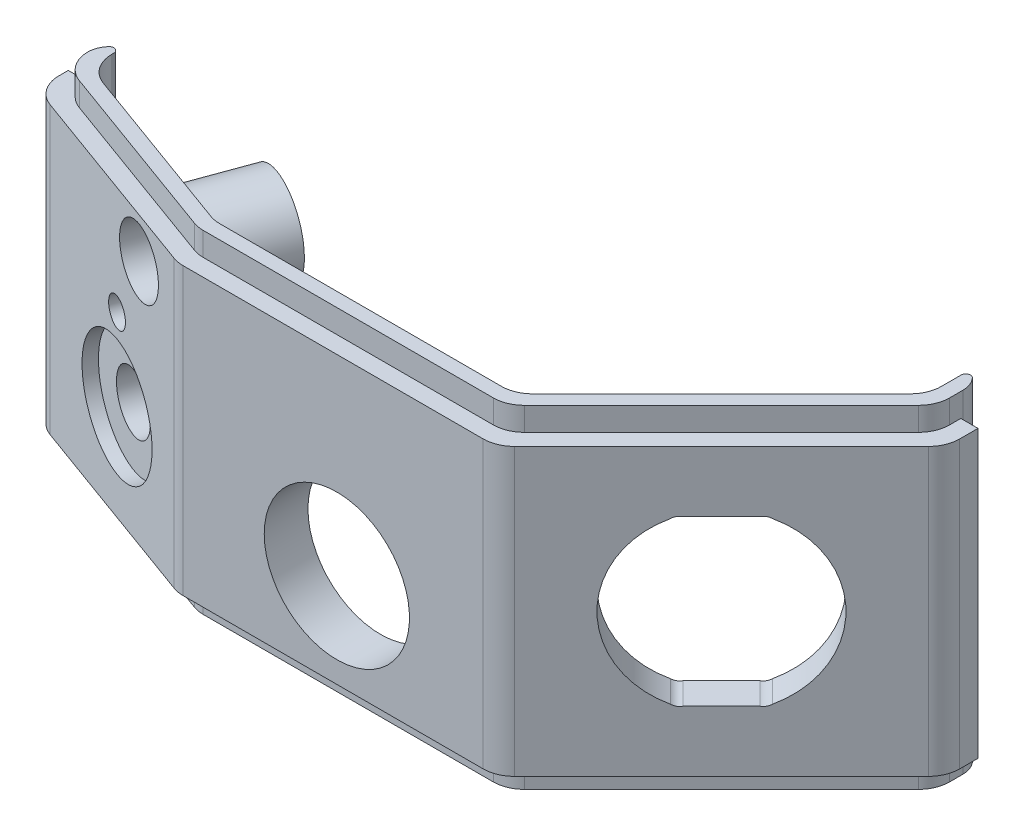
SolidWorks part; units mm, degrees
material "6061 Alloy"
ref_plane "Front Plane" through (0, 0, 0) normal (0, 0, 1) x (1, 0, 0)
ref_plane "Top Plane" through (0, 0, 0) normal (0, 1, 0) x (1, 0, 0)
ref_plane "Right Plane" through (0, 0, 0) normal (1, 0, 0) x (0, 0, -1)
sketch "Sketch1" plane through (0, 0, 0) normal (0, 1, 0) x (1, 0, 0)
  line L0 (-12.9569, 0) -> (12.9569, 0)
  line L1 (12.9569, 0) -> (31.2806, 18.3238)
  line L2 (-12.9569, 0) -> (-30.924, 6.5395)
  line L4 (28.7406, 19.3759) -> (11.9048, 2.54)
  line L5 (11.9048, 2.54) -> (-12.509, 2.54)
  line L6 (-12.509, 2.54) -> (-28.384, 8.318)
  line L8 (31.2806, 18.3238) -> (31.2806, 22.7688)
  line L9 (31.2806, 22.7688) -> (28.7406, 22.7688)
  line L10 (28.7406, 22.7688) -> (28.7406, 19.3759)
  line L11 (-28.384, 8.318) -> (-28.384, 10.9845)
  line L12 (-28.384, 10.9845) -> (-30.924, 10.9845)
  line L13 (-30.924, 10.9845) -> (-30.924, 6.5395)
  point P15 (0, 0)
  dimension "D2" = 2.54
  dimension "D3" = 135
  dimension "D6" = 4.445
  dimension "D4" = 2.54
  dimension "D7" = 2.54
  dimension "D8" = 160
  dimension "D5" = 62.2046
  dimension "D12" = 28.7406
  dimension "D13" = 4.445
  dimension "D11" = 15.875
  dimension "D9" = 17.9671
extrude "Boss-Extrude1" add sketch "Sketch1" along normal mid plane 27.305
sketch "Sketch2" plane through (0, -13.6525, 0) normal (0, -1, 0) x (1, 0, 0)
  line L9 (12.3782, -1.397) -> (30.2928, -19.3116)
  line L10 (-30.4462, -7.8523) -> (-12.7105, -1.397)
  line L11 (-12.7105, -1.397) -> (12.3782, -1.397)
  line L12 (12.3782, -1.397) -> (29.8836, -18.9024)
  line L13 (-29.527, -7.5177) -> (-12.7105, -1.397)
  line L14 (-12.7105, -1.397) -> (12.3782, -1.397)
  line L16 (-30.924, -6.5395) -> (-12.9569, 0) construction
  line L17 (-12.9569, 0) -> (12.9569, 0) construction
  line L18 (12.9569, 0) -> (31.2806, -18.3238) construction
  line L19 (-30.924, -6.5395) -> (-12.9569, 0)
  line L20 (-12.9569, 0) -> (12.9569, 0)
  line L21 (12.9569, 0) -> (31.2806, -18.3238)
  line L22 (-29.527, -7.5177) -> (-29.527, -10.9845)
  line L23 (-28.384, -10.9845) -> (-30.924, -10.9845) construction
  line L24 (-29.527, -10.9845) -> (-30.924, -10.9845)
  line L25 (-30.924, -10.9845) -> (-30.924, -6.5395)
  line L26 (31.2806, -18.3238) -> (31.2806, -22.7688)
  line L27 (31.2806, -22.7688) -> (29.8836, -22.7688)
  line L28 (31.2806, -22.7688) -> (28.7406, -22.7688) construction
  line L29 (29.8836, -22.7688) -> (29.8836, -18.9024)
  dimension "D2" = 1.397
  dimension "D1" = 1.397
extrude "Cut-Extrude1" cut sketch "Sketch2" against normal blind 2.032
sketch "Sketch17" plane through (0, -13.6525, 0) normal (0, -1, 0) x (1, 0, 0)
  line L12 (28.7406, -22.7688) -> (29.8836, -22.7688)
  line L13 (29.8836, -22.7688) -> (29.8836, -18.9024)
  line L14 (29.8836, -18.9024) -> (12.3782, -1.397)
  line L15 (12.3782, -1.397) -> (-12.7105, -1.397)
  line L16 (-12.7105, -1.397) -> (-29.527, -7.5177)
  line L17 (-29.527, -7.5177) -> (-29.527, -10.9845)
  line L18 (-29.527, -10.9845) -> (-28.384, -10.9845)
  line L19 (-28.384, -10.9845) -> (-28.384, -8.318)
  line L20 (-28.384, -8.318) -> (-12.509, -2.54)
  line L21 (-12.509, -2.54) -> (11.9048, -2.54)
  line L22 (11.9048, -2.54) -> (28.7406, -19.3759)
  line L23 (28.7406, -19.3759) -> (28.7406, -22.7688)
  line L24 (28.7406, -22.7688) -> (29.8836, -22.7688)
  line L25 (29.8836, -22.7688) -> (29.8836, -18.9024)
  line L26 (29.8836, -18.9024) -> (12.3782, -1.397)
  line L27 (12.3782, -1.397) -> (-12.7105, -1.397)
  line L28 (-12.7105, -1.397) -> (-29.527, -7.5177)
  line L29 (-29.527, -7.5177) -> (-29.527, -10.9845)
  line L30 (-29.527, -10.9845) -> (-28.384, -10.9845)
  line L31 (-28.384, -10.9845) -> (-28.384, -8.318)
  line L32 (-28.384, -8.318) -> (-12.509, -2.54)
  line L33 (-12.509, -2.54) -> (11.9048, -2.54)
  line L34 (11.9048, -2.54) -> (28.7406, -19.3759)
  line L35 (28.7406, -19.3759) -> (28.7406, -22.7688)
  dimension "D1" = 0
extrude "Cut-Extrude9" cut sketch "Sketch17" against normal blind 0.127
mirror "Mirror1" about plane through (0, 0, 0) normal (0, 1, 0) of "Cut-Extrude9", "Cut-Extrude1"
fillet "Fillet3" radius 2.54 12 edges at (29.8836, 12.573, -18.9024) (12.3782, 12.573, -1.397) (-12.7105, 12.573, -1.397) (-29.527, 12.573, -7.5177) (-29.527, -12.573, -7.5177) (-30.924, 0, -6.5395) (-12.7105, -12.573, -1.397) (-12.9569, 0, 0) (12.3782, -12.573, -1.397) (12.9569, 0, 0) (31.2806, 0, -18.3238) (29.8836, -12.573, -18.9024)
fillet "Fillet4" radius 2.54 4 edges at (-28.384, 0, -8.318) (-12.509, 0, -2.54) (11.9048, 0, -2.54) (28.7406, 0, -19.3759)
sketch "Sketch5" plane through (31.2806, 0, 0) normal (1, 0, 0) x (0, 0, -1)
  line L0 (22.7688, -11.6205) -> (19.3759, -11.6205) construction
  line L1 (22.7688, 11.6205) -> (20.8638, 11.6205)
  line L2 (22.7688, 11.6205) -> (22.7688, -11.6205)
  line L3 (22.7688, -11.6205) -> (20.8638, -11.6205)
  line L4 (20.8638, 11.6205) -> (20.8638, -11.6205)
  dimension "D1" = 1.905
extrude "Cut-Extrude4" cut sketch "Sketch5" against normal up to surface (1.397 mm away) up to face at (29.8836, 12.573, -21.3616)
sketch "Sketch6" plane through (-30.924, 0, 0) normal (-1, 0, 0) x (0, 0, 1)
  line L4 (-10.9845, 11.6205) -> (-9.0795, 11.6205)
  line L5 (-10.9845, 11.6205) -> (-10.9845, -11.6205)
  line L6 (-10.9845, -11.6205) -> (-9.0795, -11.6205)
  line L7 (-9.0795, 11.6205) -> (-9.0795, -11.6205)
  line L8 (-10.9845, 11.6205) -> (-10.9845, -11.6205) construction
  line L9 (-8.318, 11.6205) -> (-10.9845, 11.6205) construction
  line L10 (-8.318, -11.6205) -> (-10.9845, -11.6205) construction
  dimension "D1" = 1.905
extrude "Cut-Extrude5" cut sketch "Sketch6" against normal up to surface (1.397 mm away) up to face at (-29.527, 12.573, -10.1404)
sketch "Sketch32" plane through (-0.6469, 0, 1.7774) normal (0.342, 0, -0.9397) x (-0.9397, 0, -0.342)
  line L0 (27.7386, 0) -> (13.0712, 0) construction
  line L1 (27.7386, -13.5255) -> (27.7386, 13.5255) construction
  line L2 (13.0712, 13.5255) -> (13.0712, -13.5255) construction
  line L3 (20.4049, 0) -> (20.4049, -3.81) construction
  circle A0 centre (20.4049, -3.81) radius 5.9944
  dimension "D1" = 11.9888
  dimension "D2" = 3.81
extrude "Boss-Extrude4" add sketch "Sketch32" along normal blind 1.5494
hole_wizard "#12-28 Tapped Hole1" positions "Sketch12" profile "Sketch13" tap size "#12-28" standard "ANSI Inch" end condition through all
sketch "Sketch12" plane through (-0.117, 0, 0.3215) normal (-0.342, 0, 0.9397) x (0.9397, 0, 0.342)
  circle A0 centre (-20.4049, -3.81) radius 5.9944 construction
  point P0 (-20.4049, -3.81)
sketch "Sketch13" plane through (-19.2914, -3.81, -6.6574) normal (0, 1, 0) x (-0.9397, 0, -0.342)
  line L0 (0, 0) -> (0, 10.2345)
  line L1 (0, 10.2345) -> (2.3114, 10.2345)
  line L2 (2.3114, 10.2345) -> (2.3114, 0)
  line L5 (2.3114, 0) -> (0, 0)
  line L11 (0, -6.35) -> (0, 107.95) construction
  dimension "Thru Tap Drill Dia." = 4.6228
  dimension "Thru Tap Drill Depth" = 10.2345
sketch "Sketch10" plane through (-1.5157, 0, 4.1643) normal (-0.342, 0, 0.9397) x (0.9397, 0, 0.342)
  line L2 (-13.0712, -3.81) -> (-27.7386, -3.81) construction
  line L3 (-14.474, -2.411) -> (-14.474, -5.209)
  line L4 (-26.3358, -2.411) -> (-26.3358, -5.209)
  line L5 (-13.0712, 13.5255) -> (-13.0712, -13.5255) construction
  line L6 (-27.7386, -13.5255) -> (-27.7386, 13.5255) construction
  arc A0 (-14.5064, -2.1733) -> (-18.5866, 2.0351) centre (-20.4049, -3.81) ccw
  arc A1 (-19.2113, 2.8672) -> (-21.5985, 2.8672) centre (-20.4049, 2.8448) ccw
  arc A2 (-26.3034, -5.4467) -> (-14.5064, -5.4467) centre (-20.4049, -3.81) ccw
  arc A3 (-22.2233, 2.0351) -> (-26.3034, -2.1733) centre (-20.4049, -3.81) ccw
  arc A4 (-21.5985, 2.8672) -> (-22.2233, 2.0351) centre (-22.4873, 2.884) cw
  arc A5 (-19.2113, 2.8672) -> (-18.5866, 2.0351) centre (-18.3225, 2.884) ccw
  arc A6 (-14.474, -2.411) -> (-14.5064, -2.1733) centre (-15.363, -2.411) ccw
  arc A7 (-14.474, -5.209) -> (-14.5064, -5.4467) centre (-15.363, -5.209) cw
  arc A8 (-26.3358, -5.209) -> (-26.3034, -5.4467) centre (-25.4468, -5.209) ccw
  arc A9 (-26.3358, -2.411) -> (-26.3034, -2.1733) centre (-25.4468, -2.411) cw
  point P19 (-21.4256, 2.2257)
  point P24 (-14.474, -2.2948)
  point P27 (-14.474, -5.3252)
  point P30 (-26.3358, -5.3252)
  point P33 (-26.3358, -2.2948)
  point P37 (-20.4049, -3.81)
  dimension "D2" = 12.2428
  dimension "D3" = 2.3876
  dimension "D5" = 0.889
  dimension "D6" = 0.889
  dimension "D1" = 11.8618
  dimension "D4" = 6.6548
  dimension "D7" = 3.81
sketch "Sketch33" plane through (-1.5157, 0, 4.1643) normal (-0.342, 0, 0.9397) x (0.9397, 0, 0.342)
  circle A0 centre (-20.4049, -3.81) radius 4.7625
  circle A1 centre (-20.4049, 2.8448) radius 1.143
  dimension "D1" = 9.525
  dimension "D2" = 2.286
extrude "Cut-Extrude16" cut sketch "Sketch33" against normal blind 1.0414
sketch "Sketch34" plane through (0, 0, -2.54) normal (0, 0, -1) x (-1, 0, 0)
  circle A0 centre (0, -3.9751) radius 8.7503
  dimension "D1" = 17.5006
  dimension "D2" = 3.9751
extrude "Boss-Extrude5" add sketch "Sketch34" along normal blind 1.016
hole_wizard "1/2-28 Tapped Hole2" positions "Sketch19" profile "Sketch20" tap size "1/2-28" standard "ANSI Inch" end condition through all
sketch "Sketch19" plane through (0, 0, -3.556) normal (0, 0, 1) x (1, 0, 0)
  circle A0 centre (0, -3.9751) radius 8.7503 construction
  point P0 (0, -3.9751)
sketch "Sketch20" plane through (0, -3.9751, -3.556) normal (1, 0, 0) x (0, 1, 0)
  line L0 (0, 0) -> (0, 3.556)
  line L1 (0, 3.556) -> (5.9055, 3.556)
  line L2 (5.9055, 3.556) -> (5.9055, 0)
  line L5 (5.9055, 0) -> (0, 0)
  line L11 (0, -6.35) -> (0, 107.95) construction
  dimension "Thru Tap Drill Dia." = 11.811
  dimension "Thru Tap Drill Depth" = 3.556
sketch "Sketch22" plane through (6.4784, 0, 6.4784) normal (0.7071, 0, 0.7071) x (0.7071, 0, -0.7071)
  line L0 (11.2661, 0) -> (32.9714, 0) construction
  line L1 (32.9714, 13.5255) -> (32.9714, -13.5255) construction
  line L2 (11.2661, -13.5255) -> (11.2661, 13.5255) construction
  line L3 (24.6796, 6.5532) -> (19.5579, 6.5532) construction
  line L4 (24.6796, -6.5532) -> (19.5579, -6.5532) construction
  line L5 (24.3415, 6.6802) -> (19.8959, 6.6802)
  line L6 (24.3415, -6.6802) -> (19.8959, -6.6802)
  line L7 (22.1187, 0) -> (24.5225, 5.745) construction
  line L8 (24.5225, 5.745) -> (24.8834, 6.6077) construction
  line L9 (24.5225, 5.745) -> (24.5225, 6.6802) construction
  line L10 (24.7034, 6.6802) -> (24.5225, 6.6802) construction
  line L11 (24.7034, 6.6802) -> (19.534, 6.6802) construction
  line L12 (24.5225, 6.6802) -> (24.3415, 6.6802) construction
  line L13 (19.8959, 6.6802) -> (19.534, 6.6802) construction
  line L14 (19.8959, -6.6802) -> (19.534, -6.6802) construction
  line L15 (24.7034, -6.6802) -> (19.534, -6.6802) construction
  line L16 (24.7034, -6.6802) -> (24.3415, -6.6802) construction
  arc A0 (24.6796, -6.5532) -> (24.6796, 6.5532) centre (22.1187, 0) ccw construction
  arc A1 (19.5579, 6.5532) -> (19.5579, -6.5532) centre (22.1187, 0) ccw construction
  arc A2 (25.0614, -6.5304) -> (25.0614, 6.5304) centre (22.1187, 0) ccw
  arc A3 (19.176, 6.5304) -> (19.176, -6.5304) centre (22.1187, 0) ccw
  arc A4 (19.8959, 6.6802) -> (19.176, 6.5304) centre (19.715, 5.745) ccw
  arc A5 (25.0614, 6.5304) -> (24.3415, 6.6802) centre (24.5225, 5.745) ccw
  arc A6 (24.3415, -6.6802) -> (25.0614, -6.5304) centre (24.5225, -5.745) ccw
  arc A7 (19.176, -6.5304) -> (19.8959, -6.6802) centre (19.715, -5.745) ccw
  arc A8 (25.0614, 6.5304) -> (24.8834, 6.6077) centre (22.1187, 0) ccw construction
  arc A9 (24.8834, 6.6077) -> (24.7034, 6.6802) centre (22.1187, 0) ccw construction
  arc A10 (24.7034, -6.6802) -> (24.7034, 6.6802) centre (22.1187, 0) ccw construction
  arc A11 (19.534, 6.6802) -> (19.176, 6.5304) centre (22.1187, 0) ccw construction
  arc A12 (19.534, 6.6802) -> (19.534, -6.6802) centre (22.1187, 0) ccw construction
  arc A13 (19.176, -6.5304) -> (19.534, -6.6802) centre (22.1187, 0) ccw construction
  arc A14 (24.7034, -6.6802) -> (25.0614, -6.5304) centre (22.1187, 0) ccw construction
  point P4 (32.9714, 0)
  point P7 (11.2661, 0)
  dimension "D1" = 7.0358
  dimension "D4" = 1.905
  dimension "D2" = 13.1064
  dimension "D3" = 0.127
extrude "Cut-Extrude10" cut sketch "Sketch22" against normal through all
sketch "Sketch27" plane through (-0.6469, 0, 1.7774) normal (0.342, 0, -0.9397) x (-0.9397, 0, -0.342)
  line L1 (27.7386, 13.5255) -> (13.0712, 13.5255) construction
  line L4 (13.0712, 13.5255) -> (13.0712, -13.5255) construction
  circle A0 centre (17.4146, 8.3439) radius 3.7084
  circle A1 centre (17.4146, 8.3439) radius 2.6162 construction
  dimension "D1" = 1.0922
  dimension "D2" = 5.2324
  dimension "D4" = 0.635
  dimension "D3" = 5.1816
extrude "Boss-Extrude3" add sketch "Sketch27" along normal offset from surface (6.223 mm away) 8.763 up to face at (-16.2147, -3.81, -1.1858)
sketch "Sketch30" plane through (1.4815, 0, -4.0703) normal (0.342, 0, -0.9397) x (-0.9397, 0, -0.342)
  line L0 (16.1291, 10.8585) -> (18.7001, 10.8585) construction
  line L1 (18.8252, 10.4319) -> (18.8252, 10.8585) construction
  line L2 (18.8252, 10.4319) -> (19.0639, 10.7854) construction
  line L3 (18.8252, 10.4319) -> (17.4146, 8.3439) construction
  line L4 (18.8252, 10.8585) -> (18.9502, 10.8585) construction
  line L5 (18.7001, 10.8585) -> (18.8252, 10.8585) construction
  line L6 (15.879, 10.8585) -> (16.1291, 10.8585) construction
  line L7 (16.1461, 10.9855) -> (18.6831, 10.9855)
  arc A0 (15.655, 10.7072) -> (19.1742, 10.7072) centre (17.4146, 8.3439) ccw construction
  arc A1 (19.1742, 10.7072) -> (18.7001, 10.8585) centre (18.8252, 10.4319) ccw construction
  arc A2 (16.1291, 10.8585) -> (15.655, 10.7072) centre (16.004, 10.4319) ccw construction
  arc A3 (19.1742, 10.7072) -> (19.0639, 10.7854) centre (17.4146, 8.3439) ccw construction
  arc A4 (19.0639, 10.7854) -> (18.9502, 10.8585) centre (17.4146, 8.3439) ccw construction
  arc A5 (15.879, 10.8585) -> (15.655, 10.7072) centre (17.4146, 8.3439) ccw construction
  arc A7 (19.2628, 10.7995) -> (18.6831, 10.9855) centre (18.8252, 10.4319) ccw
  arc A8 (15.5664, 10.7995) -> (19.2628, 10.7995) centre (17.4146, 8.3439) ccw
  arc A9 (16.1461, 10.9855) -> (15.5664, 10.7995) centre (16.004, 10.4319) ccw
  dimension "D2" = 2.9464
  dimension "D3" = 0.889
  dimension "D1" = 5.461
  dimension "D4" = 0.127
extrude "Cut-Extrude13" cut sketch "Sketch30" against normal blind 1.143
sketch "Sketch31" plane through (1.0905, 0, -2.9962) normal (0.342, 0, -0.9397) x (-0.9397, 0, -0.342)
  line L0 (18.6831, 10.9855) -> (16.1461, 10.9855) construction
  circle A0 centre (17.4146, 8.3439) radius 2.6416
extrude "Cut-Extrude15" cut sketch "Sketch31" against normal through all
fillet "Fillet5" radius 0.7937 1 edges at (-13.5266, 8.3439, -2.9104)
fillet "Fillet6" radius 1.905 2 edges at (29.8836, 0, -22.7688) (-29.527, 0, -10.9845)
fillet "Fillet7" radius 0.381 2 edges at (28.7406, 0, -22.7688) (-28.384, 0, -10.9845)
equation "\"D2@Sketch1\"=\"D1@Sketch1\""
equation "\"D1@Sketch2\"=\"D2@Sketch2\""
